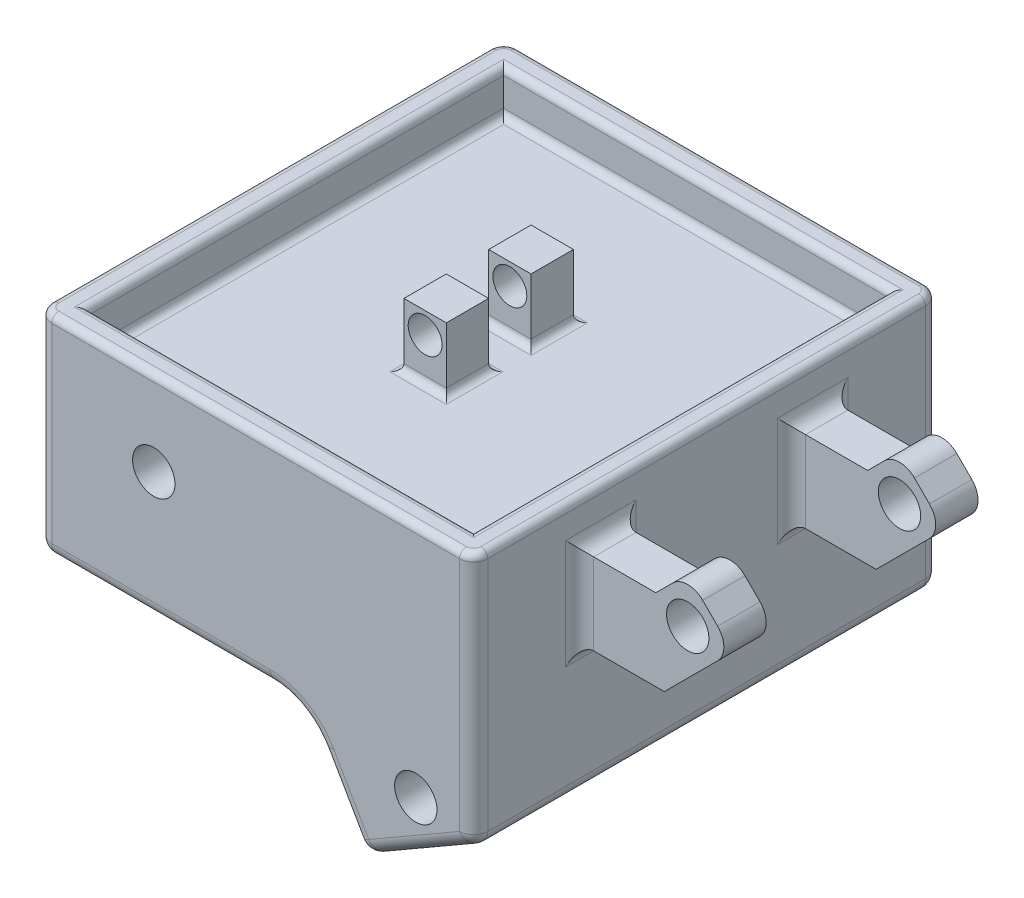
SolidWorks part; units mm, degrees
material "AISI 1020"
ref_plane "Front" through (0, 0, 0) normal (0, 0, 1) x (1, 0, 0)
ref_plane "Top" through (0, 0, 0) normal (0, 1, 0) x (1, 0, 0)
ref_plane "Right" through (0, 0, 0) normal (1, 0, 0) x (0, 0, -1)
sketch "Sketch2" plane through (0, 0, 0) normal (0, 0, 1) x (1, 0, 0)
  line L0 (0, 0) -> (139.192, 0)
  line L1 (0, 0) -> (0, 101.6)
  line L2 (0, 101.6) -> (139.192, 101.6)
  line L3 (139.192, 101.6) -> (139.192, 0)
  line L4 (69.596, 76.2) -> (0, 76.2) construction
  line L5 (69.596, 76.2) -> (139.192, 76.2) construction
  line L6 (69.596, 76.2) -> (226.7054, -14.3906) construction
  line L7 (170.0113, -17.7935) -> (236.0024, 20.3065)
  line L12 (236.0024, 20.3065) -> (261.4024, -23.6876)
  line L13 (261.4024, -23.6876) -> (195.4113, -61.7876)
  line L14 (195.4113, -61.7876) -> (170.0113, -17.7935)
  line L15 (226.7054, -14.3906) -> (239.4054, -36.3876) construction
  line L16 (226.7054, -14.3906) -> (214.0054, 7.6065) construction
  line L17 (139.192, 101.6) -> (261.4024, 101.6)
  line L18 (261.4024, 101.6) -> (261.4024, -23.6876)
  circle A1 centre (69.596, 76.2) radius 12.7
  circle A2 centre (226.7054, -14.3906) radius 12.7
  arc A3 (139.192, 0) -> (170.0113, -17.7935) centre (139.192, -35.587) cw
  point P19 (0, 0)
  point P20 (0, 0)
  point P21 (0, 0)
  dimension "D3" = 25.4
  dimension "D5" = 25.4
  dimension "D1" = 139.192
  dimension "D2" = 101.6
  dimension "D4" = 25.4
  dimension "D6" = 181.356
  dimension "D7" = 60
  dimension "D8" = 25.4
  dimension "D9" = 50.8
  dimension "D10" = 76.2
  dimension "D13" = 261.4024
extrude "Boss-Extrude1" add sketch "Sketch2" along normal blind 279.4 contours L3 L2 L1 L0 A1 | L3 A3 L7 L12 L18 L17 | L14 L13 L12 L7 A2 region at (69.596, 49.8561, 0) region at (199.0531, 49.7634, 0) region at (214.0503, -21.697, 0)
sketch "Sketch4" plane through (0, 101.6, 0) normal (0, 1, 0) x (1, 0, 0)
  line L0 (261.4024, -279.4) -> (261.4024, 0) construction
  line L1 (15.24, -264.16) -> (246.1624, -264.16)
  line L2 (15.24, -264.16) -> (15.24, -15.24)
  line L3 (15.24, -15.24) -> (246.1624, -15.24)
  line L4 (246.1624, -264.16) -> (246.1624, -15.24)
  line L5 (0, -279.4) -> (0, 0) construction
  line L6 (0, 0) -> (261.4024, 0) construction
  line L7 (0, -279.4) -> (261.4024, -279.4) construction
  line M5 (261.4024, 0) -> (0, 0)
  line M6 (0, 0) -> (0, -279.4)
  line M7 (0, -279.4) -> (261.4024, -279.4)
  line M8 (261.4024, -279.4) -> (261.4024, 0)
  dimension "D1" = 15.24
  dimension "D2" = 15.24
  dimension "D3" = 15.24
  dimension "D4" = 15.24
extrude "Boss-Extrude2" add sketch "Sketch4" along normal blind 25.4 contours L4 L1 L2 L3 M8 M5 M6 M7 region at (257.5762, 101.6, 139.7)
sketch "Sketch5" plane through (0, 0, 279.4) normal (0, 0, 1) x (1, 0, 0)
  line L0 (261.4024, 51.6562) -> (312.2024, 51.6562)
  line L1 (261.4024, 127) -> (261.4024, -23.6876) construction
  line L2 (312.2024, 51.6562) -> (344.195, 83.6488)
  line L3 (344.195, 101.6093) -> (335.2147, 110.5895)
  line L4 (317.2542, 110.5895) -> (307.1224, 100.4577)
  line L5 (307.1224, 100.4577) -> (261.4024, 100.4577)
  line L6 (261.4024, 100.4577) -> (261.4024, 51.6562)
  circle A0 centre (326.2345, 92.629) radius 12.7
  arc A1 (344.195, 101.6093) -> (344.195, 83.6488) centre (335.2147, 92.629) cw
  arc A2 (335.2147, 110.5895) -> (317.2542, 110.5895) centre (326.2345, 101.6093) ccw
  point P12 (353.1752, 92.629)
  point P15 (326.2345, 119.5698)
  dimension "D5" = 25.4
  dimension "D9" = 12.7
  dimension "D1" = 50.8
  dimension "D2" = 45.72
  dimension "D3" = 135
  dimension "D4" = 38.1
  dimension "D6" = 19.05
  dimension "D7" = 19.05
  dimension "D8" = 19.05
extrude "Boss-Extrude3" add sketch "Sketch5" against normal blind 25.4 from offset 63.5 offset against normal yes
ref_plane "Plane1" through (0, 0, 139.7) normal (0, 0, 1) x (1, 0, 0)
mirror "Mirror1" about plane through (0, 0, 139.7) normal (0, 0, 1) of "Boss-Extrude3"
sketch "Sketch6" plane through (0, 101.6, 0) normal (0, 1, 0) x (1, 0, 0)
  line L0 (-284.6475, -139.7) -> (284.6475, -139.7) construction
  line L1 (118.0012, -127) -> (143.4012, -127)
  line L2 (118.0012, -127) -> (118.0012, -101.6)
  line L3 (118.0012, -101.6) -> (143.4012, -101.6)
  line L4 (143.4012, -127) -> (143.4012, -101.6)
  line L5 (118.0012, -152.4) -> (143.4012, -152.4)
  line L6 (118.0012, -152.4) -> (118.0012, -177.8)
  line L7 (118.0012, -177.8) -> (143.4012, -177.8)
  line L8 (143.4012, -152.4) -> (143.4012, -177.8)
  line L9 (118.0012, -152.4) -> (15.24, -152.4) construction
  line L10 (15.24, -264.16) -> (15.24, -15.24) construction
  line L11 (143.4012, -152.4) -> (246.1624, -152.4) construction
  line L12 (246.1624, -264.16) -> (246.1624, -15.24) construction
  line L13 (118.0012, -127) -> (15.24, -127) construction
  line L14 (15.24, -264.16) -> (15.24, -15.24) construction
  line L15 (143.4012, -127) -> (246.1624, -127) construction
  dimension "D1" = 12.7
  dimension "D2" = 12.7
  dimension "D3" = 25.4
  dimension "D4" = 25.4
  dimension "D5" = 25.4
  dimension "D6" = 25.4
extrude "Boss-Extrude4" add sketch "Sketch6" along normal blind 38.1
sketch "Sketch7" plane through (0, 0, 177.8) normal (0, 0, 1) x (1, 0, 0)
  line L0 (118.0012, 139.7) -> (143.4012, 139.7) construction
  line L1 (118.0012, 139.7) -> (118.0012, 101.6) construction
  circle A0 centre (130.7012, 127) radius 10.16
  dimension "D1" = 20.32
  dimension "D2" = 12.7
  dimension "D3" = 12.7
extrude "Cut-Extrude1" cut sketch "Sketch7" against normal blind 76.2
scale "Scale1" scale about centroid uniform scaling yes scale factor 3
fillet "Fillet1" radius 12.7 20 edges at (105.0003, 289.1769, 558.8) (-287.1033, 289.1769, 139.7) (105.0003, 289.1769, -279.4) (497.1039, 289.1769, 139.7) (105.0003, 289.1769, -233.68) (-241.3833, 289.1769, 139.7) (105.0003, 289.1769, 513.08) (451.3839, 289.1769, 139.7) (143.1003, 212.9769, 215.9) (105.0003, 212.9769, 177.8) (66.9003, 212.9769, 215.9) (105.0003, 212.9769, 254) (143.1003, 212.9769, 63.5) (105.0003, 212.9769, 25.4) (66.9003, 212.9769, 63.5) (105.0003, 212.9769, 101.6) (105.0003, 212.9769, 513.08) (-241.3833, 212.9769, 139.7) (105.0003, 212.9769, -233.68) (451.3839, 212.9769, 139.7)
fillet "Fillet2" radius 25.4 3 edges at (497.1039, -162.8859, 139.7) (299.1305, -277.1859, 139.7) (-287.1033, -91.8231, 139.7)
fillet "Fillet3" radius 25.4 22 edges at (-283.3835, 285.4571, -275.6803) (-283.3835, 285.4571, 555.0803) (-287.1033, 105.0269, 558.8) (-287.1033, 105.0269, -279.4) (-65.6153, -91.8231, 558.8) (-279.6638, -84.3836, 558.8) (-65.6153, -91.8231, -279.4) (-279.6638, -84.3836, -279.4) (183.8533, -106.1264, 558.8) (183.8533, -106.1264, -279.4) (493.3842, 285.4571, -275.6803) (493.3842, 285.4571, 555.0803) (497.1039, 64.1278, 558.8) (493.701, -160.9212, 558.8) (402.7658, -217.3521, 558.8) (301.8536, -267.0234, 558.8) (254.6805, -200.1963, 558.8) (497.1039, 64.1278, -279.4) (493.701, -160.9212, -279.4) (402.7658, -217.3521, -279.4) (301.8536, -267.0234, -279.4) (254.6805, -200.1963, -279.4)
fillet "Fillet5" radius 25.4 8 edges at (497.1039, 63.1455, -50.8) (497.1039, 136.3478, -88.9) (497.1039, 209.5501, -50.8) (497.1039, 136.3478, -12.7) (497.1039, 209.5501, 330.2) (497.1039, 136.3478, 292.1) (497.1039, 63.1455, 330.2) (497.1039, 136.3478, 368.3)
